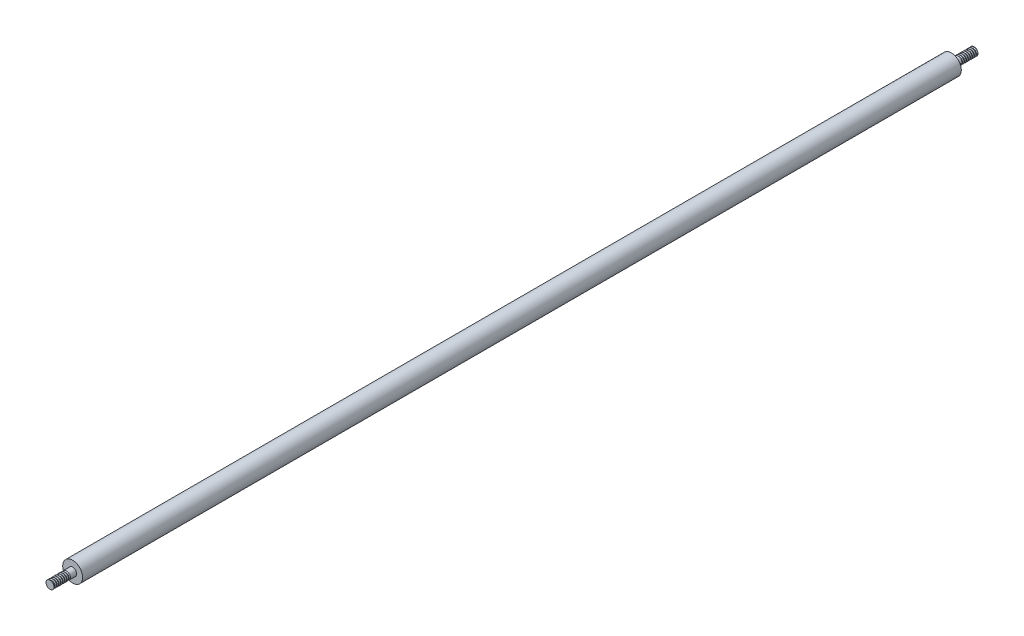
SolidWorks part; units mm, degrees
other "标注1"
sketch "草图4" plane through (2, 2, -121.95) normal (0.8691, 0.3883, -0.3062) x (-0.3792, 0.1259, -0.9167)
ref_plane "前视基准面" through (0, 0, 0) normal (0, 0, 1) x (1, 0, 0)
ref_plane "上视基准面" through (0, 0, 0) normal (0, 1, 0) x (1, 0, 0)
ref_plane "右视基准面" through (0, 0, 0) normal (1, 0, 0) x (0, 0, -1)
sketch "草图1" plane through (0, 0, 0) normal (0, 0, 1) x (1, 0, 0)
  circle A0 centre (0, 0) radius 2.5
  dimension "D1" = 5
extrude "凸台-拉伸1" add sketch "草图1" along normal mid plane 221
sketch "草图2" plane through (0, 0, 110.5) normal (0, 0, 1) x (1, 0, 0)
  circle A0 centre (0, 0) radius 1
  dimension "D1" = 2
extrude "凸台-拉伸2" add sketch "草图2" along normal blind 5.7
thread "螺纹线1" pitch 0.5 method cut profile "螺纹线轮廓1" start angle 0, offset 0, length 4, pitch 0.5, diameter 2
ref_plane "基准面1" through (-1, 0, 116.2) normal (0, -1, 0) x (-1, 0, 0)
sketch "螺纹线轮廓1" plane through (-1, 0, 116.2) normal (0, -1, 0) x (-1, 0, 0)
  line L0 (0, 0) -> (0, 0.5) construction
  line L11 (0, 0) -> (0, 0.4375)
  line L12 (0, 0.4375) -> (-0.2706, 0.2812)
  line L13 (-0.2706, 0.2812) -> (-0.2706, 0.1562)
  line L15 (-0.2706, 0.1562) -> (0, 0)
  line L17 (-0.2706, 0.2187) -> (0, 0.2187) construction
  point P2 (0, 0)
  dimension "Pitch" = 0.5
  dimension "Profile_Angle" = 60
  dimension "Profile_Land" = 0.125
  dimension "Profile_Height" = 0.2706
mirror "镜向6" about plane through (0, 0, 0) normal (0, 0, 1) of "凸台-拉伸2"
thread "螺纹线2" pitch 0.5 method cut profile "螺纹线轮廓2" start angle 0, offset 0, length 4, pitch 0.5, diameter 2
ref_plane "基准面2" through (1, 0, -116.2) normal (0, -1, 0) x (1, 0, 0)
sketch "螺纹线轮廓2" plane through (1, 0, -116.2) normal (0, -1, 0) x (1, 0, 0)
  line L0 (0, 0) -> (0, 0.5) construction
  line L11 (0, 0) -> (0, 0.4375)
  line L12 (0, 0.4375) -> (-0.2706, 0.2812)
  line L13 (-0.2706, 0.2812) -> (-0.2706, 0.1562)
  line L15 (-0.2706, 0.1562) -> (0, 0)
  line L17 (-0.2706, 0.2187) -> (0, 0.2187) construction
  point P2 (0, 0)
  dimension "Pitch" = 0.5
  dimension "Profile_Angle" = 60
  dimension "Profile_Land" = 0.125
  dimension "Profile_Height" = 0.2706
